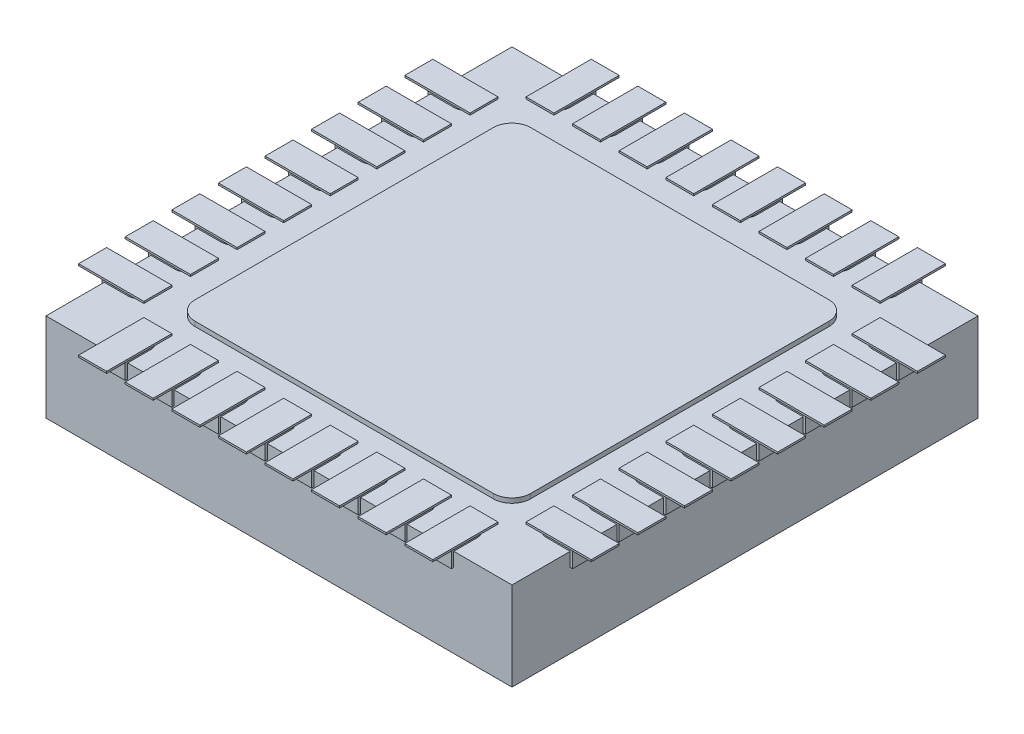
SolidWorks part; units mm, degrees
ref_plane "Front Plane" through (0, 0, 0) normal (0, 0, 1) x (1, 0, 0)
ref_plane "Top Plane" through (0, 0, 0) normal (0, 1, 0) x (1, 0, 0)
ref_plane "Right Plane" through (0, 0, 0) normal (1, 0, 0) x (0, 0, -1)
sketch "Sketch1" plane through (0, 0, 0) normal (0, 1, 0) x (1, 0, 0)
  line L0 (0, -2.75) -> (0, 2.75) construction
  line L1 (-2.525, 2.525) -> (2.525, 2.525)
  line L2 (-2.525, 2.525) -> (-2.525, -2.525)
  line L3 (-2.525, -2.525) -> (2.525, -2.525)
  line L4 (2.525, 2.525) -> (2.525, -2.525)
  line L5 (-2.75, 0) -> (2.75, 0) construction
  dimension "D1" = 5.05
  dimension "D2" = 2.525
  dimension "D3" = 2.525
sketch "Sketch2" plane through (0, 0, 0) normal (0, 1, 0) x (1, 0, 0)
  line L0 (0, -2.75) -> (0, 2.75) construction
  line L1 (-1.6, -1.8) -> (1.6, -1.8)
  line L2 (-1.8, -1.6) -> (-1.8, 1.6)
  line L3 (-1.6, 1.8) -> (1.6, 1.8)
  line L4 (1.8, -1.6) -> (1.8, 1.6)
  line L5 (-2.75, 0) -> (2.75, 0) construction
  line L6 (-1.875, -2.25) -> (-1.875, -2.525)
  line L8 (-1.875, -2.525) -> (-1.625, -2.525)
  line L9 (-1.625, -2.525) -> (-1.625, -2.25)
  line L10 (-1.875, 2.25) -> (-1.875, 2.525)
  line L12 (-1.875, 2.525) -> (-1.625, 2.525)
  line L13 (-1.625, 2.525) -> (-1.625, 2.25)
  line L14 (-1.375, -2.25) -> (-1.375, -2.525)
  line L15 (-1.125, -2.525) -> (-1.125, -2.25)
  line L16 (-1.375, -2.525) -> (-1.125, -2.525)
  line L17 (-1.125, 2.525) -> (-1.125, 2.25)
  line L18 (-1.375, 2.25) -> (-1.375, 2.525)
  line L19 (-1.375, 2.525) -> (-1.125, 2.525)
  line L20 (-0.875, -2.25) -> (-0.875, -2.525)
  line L21 (-0.625, -2.525) -> (-0.625, -2.25)
  line L22 (-0.875, -2.525) -> (-0.625, -2.525)
  line L23 (-0.625, 2.525) -> (-0.625, 2.25)
  line L24 (-0.875, 2.25) -> (-0.875, 2.525)
  line L25 (-0.875, 2.525) -> (-0.625, 2.525)
  line L26 (-0.375, -2.25) -> (-0.375, -2.525)
  line L27 (-0.125, -2.525) -> (-0.125, -2.25)
  line L28 (-0.375, -2.525) -> (-0.125, -2.525)
  line L29 (-0.125, 2.525) -> (-0.125, 2.25)
  line L30 (-0.375, 2.25) -> (-0.375, 2.525)
  line L31 (-0.375, 2.525) -> (-0.125, 2.525)
  line L32 (0.125, -2.25) -> (0.125, -2.525)
  line L33 (0.375, -2.525) -> (0.375, -2.25)
  line L34 (0.125, -2.525) -> (0.375, -2.525)
  line L35 (0.375, 2.525) -> (0.375, 2.25)
  line L36 (0.125, 2.25) -> (0.125, 2.525)
  line L37 (0.125, 2.525) -> (0.375, 2.525)
  line L38 (0.625, -2.25) -> (0.625, -2.525)
  line L39 (0.875, -2.525) -> (0.875, -2.25)
  line L40 (0.625, -2.525) -> (0.875, -2.525)
  line L41 (0.875, 2.525) -> (0.875, 2.25)
  line L42 (0.625, 2.25) -> (0.625, 2.525)
  line L43 (0.625, 2.525) -> (0.875, 2.525)
  line L44 (1.125, -2.25) -> (1.125, -2.525)
  line L45 (1.375, -2.525) -> (1.375, -2.25)
  line L46 (1.125, -2.525) -> (1.375, -2.525)
  line L47 (1.375, 2.525) -> (1.375, 2.25)
  line L48 (1.125, 2.25) -> (1.125, 2.525)
  line L49 (1.125, 2.525) -> (1.375, 2.525)
  line L50 (1.625, -2.25) -> (1.625, -2.525)
  line L51 (1.875, -2.525) -> (1.875, -2.25)
  line L52 (1.625, -2.525) -> (1.875, -2.525)
  line L53 (1.875, 2.525) -> (1.875, 2.25)
  line L54 (1.625, 2.25) -> (1.625, 2.525)
  line L55 (1.625, 2.525) -> (1.875, 2.525)
  line L56 (-2.525, -1.875) -> (-2.245, -1.875)
  line L59 (-2.245, -1.625) -> (-2.525, -1.625)
  line L60 (2.245, -1.875) -> (2.525, -1.875)
  line L62 (2.525, -1.875) -> (2.525, -1.625)
  line L63 (2.525, -1.625) -> (2.245, -1.625)
  line L64 (-2.525, -1.625) -> (-2.525, -1.875)
  line L65 (-2.245, -1.125) -> (-2.525, -1.125)
  line L66 (-2.525, -1.375) -> (-2.245, -1.375)
  line L67 (-2.525, -1.125) -> (-2.525, -1.375)
  line L68 (2.245, -1.375) -> (2.525, -1.375)
  line L69 (2.525, -1.375) -> (2.525, -1.125)
  line L70 (2.525, -1.125) -> (2.245, -1.125)
  line L71 (-2.245, -0.625) -> (-2.525, -0.625)
  line L72 (-2.525, -0.875) -> (-2.245, -0.875)
  line L73 (-2.525, -0.625) -> (-2.525, -0.875)
  line L74 (2.245, -0.875) -> (2.525, -0.875)
  line L75 (2.525, -0.875) -> (2.525, -0.625)
  line L76 (2.525, -0.625) -> (2.245, -0.625)
  line L77 (-2.245, -0.125) -> (-2.525, -0.125)
  line L78 (-2.525, -0.375) -> (-2.245, -0.375)
  line L79 (-2.525, -0.125) -> (-2.525, -0.375)
  line L80 (2.245, -0.375) -> (2.525, -0.375)
  line L81 (2.525, -0.375) -> (2.525, -0.125)
  line L82 (2.525, -0.125) -> (2.245, -0.125)
  line L83 (-2.245, 0.375) -> (-2.525, 0.375)
  line L84 (-2.525, 0.125) -> (-2.245, 0.125)
  line L85 (-2.525, 0.375) -> (-2.525, 0.125)
  line L86 (2.245, 0.125) -> (2.525, 0.125)
  line L87 (2.525, 0.125) -> (2.525, 0.375)
  line L88 (2.525, 0.375) -> (2.245, 0.375)
  line L89 (-2.245, 0.875) -> (-2.525, 0.875)
  line L90 (-2.525, 0.625) -> (-2.245, 0.625)
  line L91 (-2.525, 0.875) -> (-2.525, 0.625)
  line L92 (2.245, 0.625) -> (2.525, 0.625)
  line L93 (2.525, 0.625) -> (2.525, 0.875)
  line L94 (2.525, 0.875) -> (2.245, 0.875)
  line L95 (-2.245, 1.375) -> (-2.525, 1.375)
  line L96 (-2.525, 1.125) -> (-2.245, 1.125)
  line L97 (-2.525, 1.375) -> (-2.525, 1.125)
  line L98 (2.245, 1.125) -> (2.525, 1.125)
  line L99 (2.525, 1.125) -> (2.525, 1.375)
  line L100 (2.525, 1.375) -> (2.245, 1.375)
  line L101 (-2.245, 1.875) -> (-2.525, 1.875)
  line L102 (-2.525, 1.625) -> (-2.245, 1.625)
  line L103 (-2.525, 1.875) -> (-2.525, 1.625)
  line L104 (2.245, 1.625) -> (2.525, 1.625)
  line L105 (2.525, 1.625) -> (2.525, 1.875)
  line L106 (2.525, 1.875) -> (2.245, 1.875)
  line L107 (-2.245, -1.625) -> (-2.245, -1.125) construction
  line L108 (-2.525, 2.525) -> (-2.525, -2.525) construction
  line L109 (-2.525, 2.525) -> (2.525, 2.525) construction
  line L110 (-2.525, -2.525) -> (2.525, -2.525) construction
  line L111 (2.525, 2.525) -> (2.525, -2.525) construction
  arc A0 (1.6, 1.8) -> (1.8, 1.6) centre (1.6, 1.6) cw
  arc A1 (-1.8, 1.6) -> (-1.6, 1.8) centre (-1.6, 1.6) cw
  arc A2 (-1.6, -1.8) -> (-1.8, -1.6) centre (-1.6, -1.6) cw
  arc A3 (1.6, -1.8) -> (1.8, -1.6) centre (1.6, -1.6) ccw
  arc A4 (-1.625, -2.25) -> (-1.875, -2.25) centre (-1.75, -2.25) ccw
  arc A5 (-1.875, 2.25) -> (-1.625, 2.25) centre (-1.75, 2.25) ccw
  arc A6 (-1.125, -2.25) -> (-1.375, -2.25) centre (-1.25, -2.25) ccw
  arc A7 (-1.375, 2.25) -> (-1.125, 2.25) centre (-1.25, 2.25) ccw
  arc A8 (-0.625, -2.25) -> (-0.875, -2.25) centre (-0.75, -2.25) ccw
  arc A9 (-0.875, 2.25) -> (-0.625, 2.25) centre (-0.75, 2.25) ccw
  arc A10 (-0.125, -2.25) -> (-0.375, -2.25) centre (-0.25, -2.25) ccw
  arc A11 (-0.375, 2.25) -> (-0.125, 2.25) centre (-0.25, 2.25) ccw
  arc A12 (0.375, -2.25) -> (0.125, -2.25) centre (0.25, -2.25) ccw
  arc A13 (0.125, 2.25) -> (0.375, 2.25) centre (0.25, 2.25) ccw
  arc A14 (0.875, -2.25) -> (0.625, -2.25) centre (0.75, -2.25) ccw
  arc A15 (0.625, 2.25) -> (0.875, 2.25) centre (0.75, 2.25) ccw
  arc A16 (1.375, -2.25) -> (1.125, -2.25) centre (1.25, -2.25) ccw
  arc A17 (1.125, 2.25) -> (1.375, 2.25) centre (1.25, 2.25) ccw
  arc A18 (1.875, -2.25) -> (1.625, -2.25) centre (1.75, -2.25) ccw
  arc A19 (1.625, 2.25) -> (1.875, 2.25) centre (1.75, 2.25) ccw
  arc A20 (-2.245, -1.875) -> (-2.245, -1.625) centre (-2.245, -1.75) ccw
  arc A21 (2.245, -1.625) -> (2.245, -1.875) centre (2.245, -1.75) ccw
  arc A22 (-2.245, -1.375) -> (-2.245, -1.125) centre (-2.245, -1.25) ccw
  arc A23 (2.245, -1.125) -> (2.245, -1.375) centre (2.245, -1.25) ccw
  arc A24 (-2.245, -0.875) -> (-2.245, -0.625) centre (-2.245, -0.75) ccw
  arc A25 (2.245, -0.625) -> (2.245, -0.875) centre (2.245, -0.75) ccw
  arc A26 (-2.245, -0.375) -> (-2.245, -0.125) centre (-2.245, -0.25) ccw
  arc A27 (2.245, -0.125) -> (2.245, -0.375) centre (2.245, -0.25) ccw
  arc A28 (-2.245, 0.125) -> (-2.245, 0.375) centre (-2.245, 0.25) ccw
  arc A29 (2.245, 0.375) -> (2.245, 0.125) centre (2.245, 0.25) ccw
  arc A30 (-2.245, 0.625) -> (-2.245, 0.875) centre (-2.245, 0.75) ccw
  arc A31 (2.245, 0.875) -> (2.245, 0.625) centre (2.245, 0.75) ccw
  arc A32 (-2.245, 1.125) -> (-2.245, 1.375) centre (-2.245, 1.25) ccw
  arc A33 (2.245, 1.375) -> (2.245, 1.125) centre (2.245, 1.25) ccw
  arc A34 (-2.245, 1.625) -> (-2.245, 1.875) centre (-2.245, 1.75) ccw
  arc A35 (2.245, 1.875) -> (2.245, 1.625) centre (2.245, 1.75) ccw
  point P14 (-1.8, -1.8)
  point P17 (1.8, -1.8)
  dimension "D5" = 0.2
  dimension "D1" = 3.6
  dimension "D2" = 1.8
  dimension "D3" = 1.8
  dimension "D4" = 1.8
  dimension "D6" = 0.25
  dimension "D7" = 0.275
  dimension "D8" = 1.75
  dimension "D10" = 0.5
  dimension "D11" = 1.75
  dimension "D12" = 0.25
  dimension "D13" = 0.28
  dimension "D15" = 0.5
  dimension "D9" = 8
  dimension "D14" = 8
sketch "Sketch3" plane through (0, 0, 0) normal (0, 1, 0) x (1, 0, 0)
  line L0 (0, -2.7775) -> (0, 2.7775) construction
  line L1 (2.5, 2.5) -> (-2.5, 2.5)
  line L2 (2.5, 2.5) -> (2.5, -2.5)
  line L3 (2.5, -2.5) -> (-2.5, -2.5)
  line L4 (-2.5, 2.5) -> (-2.5, -2.5)
  line L5 (-2.7775, 0) -> (2.7775, 0) construction
  dimension "D1" = 5
  dimension "D2" = 2.5
  dimension "D3" = 2.5
  dimension "D4" = 2.5
extrude "Boss-Extrude2" add sketch "Sketch3" against normal blind 0.95
extrude "Boss-Extrude3" add sketch "Sketch2" along normal blind 0.05 and the other way blind 0.15
ref_plane "Plane1" through (0, 0.06, 0) normal (0, 1, 0) x (1, 0, 0)
sketch "Sketch4" plane through (0, 0.06, 0) normal (0, 1, 0) x (1, 0, 0)
  line L0 (-0.5555, 0) -> (0.5555, 0) construction
  line L1 (-1.9, 2.75) -> (-1.6, 2.75)
  line L2 (-1.9, 2.75) -> (-1.9, 2.05)
  line L3 (-1.9, 2.05) -> (-1.6, 2.05)
  line L4 (-1.6, 2.75) -> (-1.6, 2.05)
  line L5 (-1.9, -2.05) -> (-1.6, -2.05)
  line L6 (-1.9, -2.05) -> (-1.9, -2.75)
  line L7 (-1.9, -2.75) -> (-1.6, -2.75)
  line L8 (-1.6, -2.05) -> (-1.6, -2.75)
  line L9 (0, -0.5555) -> (0, 0.5555) construction
  line L10 (-1.4, -2.75) -> (-1.1, -2.75)
  line L11 (-1.1, -2.05) -> (-1.1, -2.75)
  line L12 (-1.4, -2.05) -> (-1.4, -2.75)
  line L13 (-1.4, -2.05) -> (-1.1, -2.05)
  line L14 (-1.4, 2.75) -> (-1.4, 2.05)
  line L15 (-1.4, 2.05) -> (-1.1, 2.05)
  line L16 (-1.1, 2.75) -> (-1.1, 2.05)
  line L17 (-1.4, 2.75) -> (-1.1, 2.75)
  line L18 (-0.9, -2.75) -> (-0.6, -2.75)
  line L19 (-0.6, -2.05) -> (-0.6, -2.75)
  line L20 (-0.9, -2.05) -> (-0.9, -2.75)
  line L21 (-0.9, -2.05) -> (-0.6, -2.05)
  line L22 (-0.9, 2.75) -> (-0.9, 2.05)
  line L23 (-0.9, 2.05) -> (-0.6, 2.05)
  line L24 (-0.6, 2.75) -> (-0.6, 2.05)
  line L25 (-0.9, 2.75) -> (-0.6, 2.75)
  line L26 (-0.4, -2.75) -> (-0.1, -2.75)
  line L27 (-0.1, -2.05) -> (-0.1, -2.75)
  line L28 (-0.4, -2.05) -> (-0.4, -2.75)
  line L29 (-0.4, -2.05) -> (-0.1, -2.05)
  line L30 (-0.4, 2.75) -> (-0.4, 2.05)
  line L31 (-0.4, 2.05) -> (-0.1, 2.05)
  line L32 (-0.1, 2.75) -> (-0.1, 2.05)
  line L33 (-0.4, 2.75) -> (-0.1, 2.75)
  line L34 (0.1, -2.75) -> (0.4, -2.75)
  line L35 (0.4, -2.05) -> (0.4, -2.75)
  line L36 (0.1, -2.05) -> (0.1, -2.75)
  line L37 (0.1, -2.05) -> (0.4, -2.05)
  line L38 (0.1, 2.75) -> (0.1, 2.05)
  line L39 (0.1, 2.05) -> (0.4, 2.05)
  line L40 (0.4, 2.75) -> (0.4, 2.05)
  line L41 (0.1, 2.75) -> (0.4, 2.75)
  line L42 (0.6, -2.75) -> (0.9, -2.75)
  line L43 (0.9, -2.05) -> (0.9, -2.75)
  line L44 (0.6, -2.05) -> (0.6, -2.75)
  line L45 (0.6, -2.05) -> (0.9, -2.05)
  line L46 (0.6, 2.75) -> (0.6, 2.05)
  line L47 (0.6, 2.05) -> (0.9, 2.05)
  line L48 (0.9, 2.75) -> (0.9, 2.05)
  line L49 (0.6, 2.75) -> (0.9, 2.75)
  line L50 (1.1, -2.75) -> (1.4, -2.75)
  line L51 (1.4, -2.05) -> (1.4, -2.75)
  line L52 (1.1, -2.05) -> (1.1, -2.75)
  line L53 (1.1, -2.05) -> (1.4, -2.05)
  line L54 (1.1, 2.75) -> (1.1, 2.05)
  line L55 (1.1, 2.05) -> (1.4, 2.05)
  line L56 (1.4, 2.75) -> (1.4, 2.05)
  line L57 (1.1, 2.75) -> (1.4, 2.75)
  line L58 (1.6, -2.75) -> (1.9, -2.75)
  line L59 (1.9, -2.05) -> (1.9, -2.75)
  line L60 (1.6, -2.05) -> (1.6, -2.75)
  line L61 (1.6, -2.05) -> (1.9, -2.05)
  line L62 (1.6, 2.75) -> (1.6, 2.05)
  line L63 (1.6, 2.05) -> (1.9, 2.05)
  line L64 (1.9, 2.75) -> (1.9, 2.05)
  line L65 (1.6, 2.75) -> (1.9, 2.75)
  line L66 (-1.9, -2.75) -> (-1.4, -2.75) construction
  line L67 (-2.75, 1.1) -> (-2.05, 1.1)
  line L68 (-2.75, 1.9) -> (-2.05, 1.9)
  line L69 (-2.75, 1.9) -> (-2.75, 1.6)
  line L70 (-2.75, 1.6) -> (-2.05, 1.6)
  line L71 (-2.05, 1.9) -> (-2.05, 1.6)
  line L72 (2.05, 1.9) -> (2.75, 1.9)
  line L73 (2.05, 1.9) -> (2.05, 1.6)
  line L74 (2.05, 1.6) -> (2.75, 1.6)
  line L75 (2.75, 1.9) -> (2.75, 1.6)
  line L76 (-2.05, 1.4) -> (-2.05, 1.1)
  line L77 (-2.75, 1.4) -> (-2.05, 1.4)
  line L78 (-2.75, 1.4) -> (-2.75, 1.1)
  line L79 (2.05, 1.4) -> (2.75, 1.4)
  line L80 (2.75, 1.4) -> (2.75, 1.1)
  line L81 (2.05, 1.1) -> (2.75, 1.1)
  line L82 (2.05, 1.4) -> (2.05, 1.1)
  line L83 (-2.75, 0.6) -> (-2.05, 0.6)
  line L84 (-2.05, 0.9) -> (-2.05, 0.6)
  line L85 (-2.75, 0.9) -> (-2.05, 0.9)
  line L86 (-2.75, 0.9) -> (-2.75, 0.6)
  line L87 (2.05, 0.9) -> (2.75, 0.9)
  line L88 (2.75, 0.9) -> (2.75, 0.6)
  line L89 (2.05, 0.6) -> (2.75, 0.6)
  line L90 (2.05, 0.9) -> (2.05, 0.6)
  line L91 (-2.75, 0.1) -> (-2.05, 0.1)
  line L92 (-2.05, 0.4) -> (-2.05, 0.1)
  line L93 (-2.75, 0.4) -> (-2.05, 0.4)
  line L94 (-2.75, 0.4) -> (-2.75, 0.1)
  line L95 (2.05, 0.4) -> (2.75, 0.4)
  line L96 (2.75, 0.4) -> (2.75, 0.1)
  line L97 (2.05, 0.1) -> (2.75, 0.1)
  line L98 (2.05, 0.4) -> (2.05, 0.1)
  line L99 (-2.75, -0.4) -> (-2.05, -0.4)
  line L100 (-2.05, -0.1) -> (-2.05, -0.4)
  line L101 (-2.75, -0.1) -> (-2.05, -0.1)
  line L102 (-2.75, -0.1) -> (-2.75, -0.4)
  line L103 (2.05, -0.1) -> (2.75, -0.1)
  line L104 (2.75, -0.1) -> (2.75, -0.4)
  line L105 (2.05, -0.4) -> (2.75, -0.4)
  line L106 (2.05, -0.1) -> (2.05, -0.4)
  line L107 (-2.75, -0.9) -> (-2.05, -0.9)
  line L108 (-2.05, -0.6) -> (-2.05, -0.9)
  line L109 (-2.75, -0.6) -> (-2.05, -0.6)
  line L110 (-2.75, -0.6) -> (-2.75, -0.9)
  line L111 (2.05, -0.6) -> (2.75, -0.6)
  line L112 (2.75, -0.6) -> (2.75, -0.9)
  line L113 (2.05, -0.9) -> (2.75, -0.9)
  line L114 (2.05, -0.6) -> (2.05, -0.9)
  line L115 (-2.75, -1.4) -> (-2.05, -1.4)
  line L116 (-2.05, -1.1) -> (-2.05, -1.4)
  line L117 (-2.75, -1.1) -> (-2.05, -1.1)
  line L118 (-2.75, -1.1) -> (-2.75, -1.4)
  line L119 (2.05, -1.1) -> (2.75, -1.1)
  line L120 (2.75, -1.1) -> (2.75, -1.4)
  line L121 (2.05, -1.4) -> (2.75, -1.4)
  line L122 (2.05, -1.1) -> (2.05, -1.4)
  line L123 (-2.75, -1.9) -> (-2.05, -1.9)
  line L124 (-2.05, -1.6) -> (-2.05, -1.9)
  line L125 (-2.75, -1.6) -> (-2.05, -1.6)
  line L126 (-2.75, -1.6) -> (-2.75, -1.9)
  line L127 (2.05, -1.6) -> (2.75, -1.6)
  line L128 (2.75, -1.6) -> (2.75, -1.9)
  line L129 (2.05, -1.9) -> (2.75, -1.9)
  line L130 (2.05, -1.6) -> (2.05, -1.9)
  line L131 (-2.75, 1.6) -> (-2.75, 1.1) construction
  dimension "D1" = 0.3
  dimension "D2" = 0.7
  dimension "D3" = 5.5
  dimension "D4" = 2.75
  dimension "D5" = 1.9
  dimension "D7" = 0.5
  dimension "D8" = 2.75
  dimension "D9" = 5.5
  dimension "D10" = 1.9
  dimension "D11" = 0.3
  dimension "D12" = 0.7
  dimension "D14" = 0.5
  dimension "D6" = 8
  dimension "D13" = 8
extrude "Boss-Extrude4" add sketch "Sketch4" against normal blind 0.02
sketch "Sketch6" plane through (0, -0.95, 0) normal (0, -1, 0) x (1, 0, 0)
  line L0 (1.3, -1) -> (-2.5951, -1) construction
  line L1 (1.3, 0.8) -> (-2.5951, 0.8) construction
  line L2 (1.3, -0.1) -> (-2.5951, -0.1) construction
  line L3 (0, -0.5555) -> (0, 0.5555) construction
  line L4 (0.5555, 0) -> (-0.5555, 0) construction
  line L5 (1.3, 1.7) -> (-2.5967, 1.7) construction
  text T0 "CC2540" font "SWRomnd" height 0.55
  text T1 "F256" font "SWRomnd" height 0.55
  text T2 "TI 58J\r\n" font "SWRomnd" height 0.55
  text T3 "P9FN G4" font "SWRomnd" height 0.5
  dimension "D1" = 1.3
  dimension "D2" = 1
  dimension "D3" = 0.9
  dimension "D4" = 0.9
  dimension "D5" = 0.9
extrude "Cut-Extrude1" cut sketch "Sketch6" against normal blind 0.05
sketch "Sketch7" plane through (0, -0.95, 0) normal (0, -1, 0) x (1, 0, 0)
  line L0 (0, -0.5555) -> (0, 0.5555) construction
  line L1 (0.5555, 0) -> (-0.5555, 0) construction
  circle A0 centre (1.75, -1.75) radius 0.3
  dimension "D1" = 0.6
  dimension "D2" = 1.75
  dimension "D3" = 1.75
extrude "Cut-Extrude3" cut sketch "Sketch7" against normal blind 0.1
equation "\"D2@Sketch1\"=\"D1@Sketch1\"/2"
equation "\"D3@Sketch1\"=\"D1@Sketch1\"/2"
